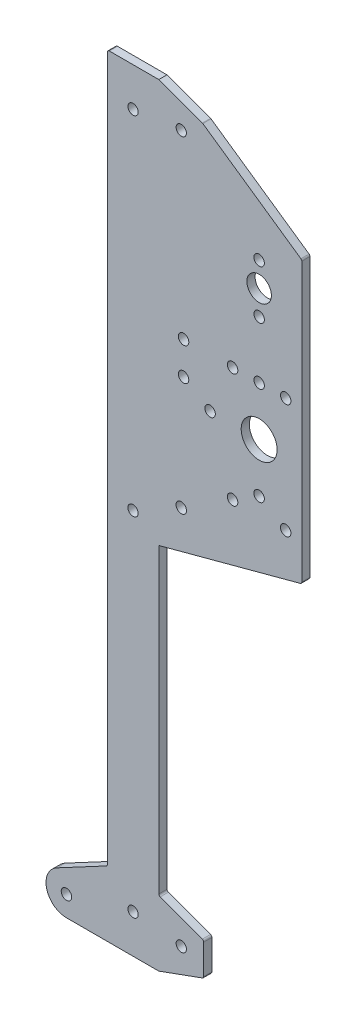
SolidWorks part; units mm, degrees
ref_plane "Front Plane" through (0, 0, 0) normal (0, 0, 1) x (1, 0, 0)
ref_plane "Top Plane" through (0, 0, 0) normal (0, 1, 0) x (1, 0, 0)
ref_plane "Right Plane" through (0, 0, 0) normal (1, 0, 0) x (0, 0, -1)
sketch "Sketch1" plane through (0, 0, 0) normal (0, 0, 1) x (1, 0, 0)
  line L1 (-10, 150) -> (10, 150)
  line L2 (-10, 150) -> (-10, -150)
  line L3 (-10, -150) -> (10, -150)
  line L4 (10, 150) -> (10, -150)
  line L5 (-10, 150) -> (10, -150) construction
  line L6 (-10, -150) -> (10, 150) construction
  point P0 (0, 0)
  dimension "D1" = 300
  dimension "20mm" = 20
extrude "Boss-Extrude1" add sketch "Sketch1" along normal blind 3.175
sketch "Sketch2" plane through (0, 0, 3.175) normal (0, 0, 1) x (1, 0, 0)
  line L0 (10, 150) -> (27.4625, 143.65)
  line L1 (27.4625, 143.65) -> (27.4625, 130.95)
  line L2 (27.4625, 130.95) -> (10, 124.6)
  line L3 (10, -150) -> (10, 150) construction
  line L4 (10, 124.6) -> (10, 150)
  line L5 (10, 150) -> (-10, 150) construction
  line L6 (-10, 0) -> (10, 0) construction
  line L7 (-10, 150) -> (-10, -150) construction
  line L8 (10, -124.6) -> (10, -150)
  line L9 (27.4625, -130.95) -> (10, -124.6)
  line L10 (27.4625, -143.65) -> (27.4625, -130.95)
  line L11 (10, -150) -> (27.4625, -143.65)
  line L12 (18.7312, 140.475) -> (18.7312, 134.125) construction
  circle A1 centre (18.7312, 134.125) radius 5 construction
  circle A2 centre (18.7312, 140.475) radius 2 construction
  circle A4 centre (18.7312, -134.125) radius 5 construction
  circle A5 centre (18.7312, -134.125) radius 2 construction
  circle A6 centre (18.7312, 137.3) radius 2
  circle A7 centre (18.7312, -137.3) radius 2
  point P3 (27.4625, 137.3)
  point P8 (10, 137.3)
  point P13 (18.7312, 127.775)
  point P31 (27.4625, -137.3)
  dimension "D3" = 4
  dimension "D4" = 10
  dimension "D1" = 17.4625
  dimension "2.5" = 25.4
  dimension "D2" = 12.7
  dimension "D5" = 9.525
  dimension "D6" = 9.525
extrude "Boss-Extrude2" add sketch "Sketch2" against normal up to surface (3.175 mm away) up to face at (0, 0, 0)
sketch "Sketch4" plane through (0, 0, 3.175) normal (0, 0, 1) x (1, 0, 0)
  line L0 (0, 150) -> (0, 135) construction
  line L2 (0, 135) -> (0, 0) construction
  line L3 (0, 0) -> (0, -135) construction
  line L4 (0, -135) -> (0, -150) construction
  line L6 (10, 150) -> (-10, 150) construction
  line L7 (-10, -150) -> (10, -150) construction
  circle A0 centre (0, -135) radius 2
  circle A1 centre (0, 0) radius 2
  circle A2 centre (0, 135) radius 2
  dimension "D4" = 4
  dimension "D1" = 15
  dimension "D2" = 135
  dimension "D3" = 135
extrude "Cut-Extrude1" cut sketch "Sketch4" against normal through all
sketch "Sketch5" plane through (0, 0, 3.175) normal (0, 0, 1) x (1, 0, 0)
  line L0 (-10, 111.9) -> (-41.75, 118.25)
  line L1 (-10, 150) -> (-10, -150) construction
  line L2 (-41.75, 118.25) -> (-41.75, 137.3)
  line L3 (-41.75, 137.3) -> (-10, 137.3)
  line L4 (-10, 137.3) -> (-10, 111.9)
  line L5 (10, 150) -> (-10, 150) construction
  line L6 (-41.75, 133.3313) -> (-37.7813, 133.3313) construction
  line L7 (-13.9688, 133.3313) -> (-10, 133.3313) construction
  line L8 (-10, -150) -> (-25.875, -150)
  line L9 (-29.6103, -135.0588) -> (-10, -124.6)
  line L10 (-10, -124.6) -> (-10, -150)
  circle A0 centre (-13.9688, 133.3313) radius 2.032
  circle A1 centre (-13.9688, 122.2188) radius 2.032
  circle A2 centre (-37.7813, 133.3313) radius 2.032
  circle A3 centre (-37.7813, 122.2188) radius 2.032
  arc A4 (-25.875, -150) -> (-29.6103, -135.0588) centre (-25.875, -142.0625) cw
  circle A5 centre (-25.875, -142.0625) radius 2.032
  point P24 (-25.875, 137.3)
  dimension "D5" = 4.064
  dimension "D9" = 4.064
  dimension "D10" = 7.9375
  dimension "D1" = 12.7
  dimension "D2" = 19.05
  dimension "D3" = 25.4
  dimension "D4" = 31.75
  dimension "D6" = 11.1125
  dimension "D7" = 23.8125
  dimension "D8" = 3.9688
  dimension "D11" = 25.4
extrude "Boss-Extrude3" [suppressed] add sketch "Sketch5" against normal up to surface (1.5875 mm away) up to face at (2, -135, 0)
fillet "Fillet3" [suppressed] radius 1.5875
sketch "Sketch6" plane through (0, 0, 3.175) normal (0, 0, 1) x (1, 0, 0)
  line L0 (-10, -124.6) -> (-10, -150) construction
  line L1 (-10, -150) -> (-25.875, -150) construction
  line L2 (-29.6103, -135.0588) -> (-10, -124.6) construction
  line L3 (-10, -124.6) -> (-10, -150)
  line L4 (-10, -150) -> (-25.875, -150)
  line L5 (-29.6103, -135.0588) -> (-10, -124.6)
  circle A0 centre (-25.875, -142.0625) radius 2.032 construction
  arc A1 (-29.6103, -135.0588) -> (-25.875, -150) centre (-25.875, -142.0625) ccw construction
  circle A2 centre (-25.875, -142.0625) radius 2.032
  arc A3 (-29.6103, -135.0588) -> (-25.875, -150) centre (-25.875, -142.0625) ccw
extrude "Boss-Extrude4" add sketch "Sketch6" against normal up to vertex (3.175 mm away) up to point (-10, -150, 0)
fillet "Fillet4" radius 0.7937 8 edges at (10, 124.6, 1.5875) (27.4625, 130.95, 1.5875) (-10, 150, 1.5875) (27.4625, 143.65, 1.5875) (-10, -124.6, 1.5875) (10, -124.6, 1.5875) (27.4625, -130.95, 1.5875) (27.4625, -143.65, 1.5875)
fillet "Fillet5" [suppressed] radius 1.5875
sketch "Sketch7" plane through (0, 0, 0) normal (0, 0, -1) x (-1, 0, 0)
  line L0 (-27.1212, 143.7462) -> (-65.2212, 117.3147)
  line L1 (-65.5625, 116.6625) -> (-65.5625, 8.7125)
  line L2 (-64.9742, 7.9458) -> (-10, -6.7845)
  line L4 (-10, -6.7845) -> (-10, 124.044)
  line L5 (-27.4625, 143.094) -> (-27.4625, 131.506) construction
  line L6 (-26.94, 130.76) -> (-10.5225, 124.79) construction
  line L7 (-27.4625, 143.094) -> (-27.4625, 131.506)
  line L8 (-26.94, 130.76) -> (-10.5225, 124.79)
  line L9 (-10, 150) -> (9.2063, 150) construction
  line L10 (-10, 150) -> (9.2063, 150) construction
  line L11 (-48.989, 45.225) -> (-48.989, 48.4) construction
  line L12 (-38.6703, 23) -> (-59.3078, 23) construction
  line L13 (-38.6703, 23) -> (-38.6703, 67.45) construction
  line L14 (-38.6703, 67.45) -> (-59.3078, 67.45) construction
  line L15 (-59.3078, 23) -> (-59.3078, 67.45) construction
  line L16 (-38.6703, 23) -> (-59.3078, 67.45) construction
  line L17 (-38.6703, 67.45) -> (-59.3078, 23) construction
  line L18 (-48.989, 99.2) -> (-48.989, 48.4) construction
  line L19 (-10, -124.044) -> (-10, 124.044) construction
  arc A0 (-65.2212, 117.3147) -> (-65.5625, 116.6625) centre (-64.7688, 116.6625) ccw
  arc A1 (-65.5625, 8.7125) -> (-64.9742, 7.9458) centre (-64.7687, 8.7125) ccw
  arc A2 (-26.94, 143.84) -> (-27.4625, 143.094) centre (-26.6688, 143.094) ccw construction
  arc A3 (-27.4625, 131.506) -> (-26.94, 130.76) centre (-26.6688, 131.506) ccw construction
  arc A4 (-10, 124.044) -> (-10.5225, 124.79) centre (-10.7937, 124.044) ccw construction
  arc A5 (-27.1212, 143.7462) -> (-27.4625, 143.094) centre (-26.6688, 143.094) ccw
  arc A6 (-27.4625, 131.506) -> (-26.94, 130.76) centre (-26.6688, 131.506) ccw
  arc A7 (-10, 124.044) -> (-10.5225, 124.79) centre (-10.7937, 124.044) ccw
  arc A8 (10, 149.2063) -> (9.2063, 150) centre (9.2063, 149.2063) ccw construction
  circle A9 centre (-48.989, 99.2) radius 4.7625
  circle A10 centre (-48.989, 48.4) radius 6.985
  circle A11 centre (-59.3078, 67.45) radius 2.032
  circle A12 centre (-59.3078, 23) radius 2.032
  circle A13 centre (-38.6703, 23) radius 2.032
  circle A14 centre (-38.6703, 67.45) radius 2.032
  circle A15 centre (-18.7312, 10.3) radius 2.032
  point P32 (-48.989, 45.225)
  point P42 (0, 0)
  point P45 (-18.7312, 137.3)
  dimension "D4" = 9.525
  dimension "D6" = 13.97
  dimension "D11" = 4.064
  dimension "D1" = 38.1
  dimension "D2" = 107.95
  dimension "D3" = 16.5735
  dimension "D5" = 50.8
  dimension "D7" = 3.175
  dimension "D8" = 44.45
  dimension "D9" = 50.8
  dimension "D10" = 20.6375
  dimension "D12" = 75
  dimension "D13" = 127
  dimension "D14" = 33.3375
extrude "Boss-Extrude5" add sketch "Sketch7" against normal up to surface (3.175 mm away) up to face at (2, -135, 3.175)
sketch "Sketch8" plane through (0, 0, 3.175) normal (0, 0, 1) x (1, 0, 0)
  line L0 (48.989, 48.4) -> (48.989, 67.45) construction
  line L1 (48.989, 48.4) -> (29.939, 48.4) construction
  line L2 (48.989, 48.4) -> (48.989, 29.35) construction
  line L3 (48.989, 99.2) -> (48.989, 108.725) construction
  line L4 (48.989, 99.2) -> (48.989, 89.675) construction
  line L5 (19.6203, 67.45) -> (19.6203, 54.75) construction
  circle A0 centre (48.989, 67.45) radius 2.032
  circle A1 centre (29.939, 48.4) radius 2.032
  circle A2 centre (48.989, 29.35) radius 2.032
  circle A3 centre (59.3078, 67.45) radius 2.032 construction
  circle A4 centre (48.989, 108.725) radius 2.032
  circle A5 centre (48.989, 89.675) radius 2.032
  circle A6 centre (19.6203, 54.75) radius 2.032
  circle A7 centre (19.6203, 67.45) radius 2.032
  dimension "D2" = 9.525
  dimension "D1" = 19.05
  dimension "D3" = 12.7
  dimension "D4" = 6.35
  dimension "D5" = 10.3187
extrude "Cut-Extrude2" cut sketch "Sketch8" against normal through all
